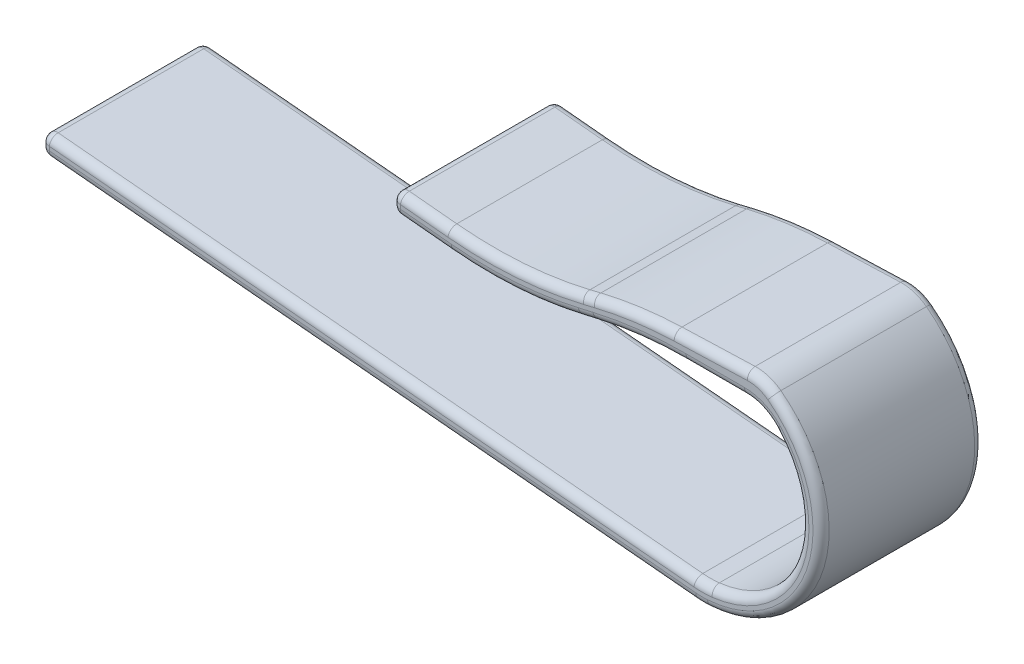
SolidWorks part; units mm, degrees
ref_plane "Front Plane" through (0, 0, 0) normal (0, 0, 1) x (1, 0, 0)
ref_plane "Top Plane" through (0, 0, 0) normal (0, 1, 0) x (1, 0, 0)
ref_plane "Right Plane" through (0, 0, 0) normal (1, 0, 0) x (0, 0, -1)
sketch "Sketch1" plane through (0, 0, 0) normal (0, 0, 1) x (1, 0, 0)
  line L7 (0, -7.5) -> (81.4654, -15)
  line L8 (0, -5) -> (81.4654, -12.5)
  line L11 (0, -5) -> (0, -7.5)
  line L12 (74.0454, 10.0596) -> (88.8853, 10.0596)
  line L13 (73.1738, 12.5) -> (88.8853, 13.0363)
  line L14 (43.4402, 10.4683) -> (43.4402, 7.9683)
  line L15 (43.4402, 10.4683) -> (58.7428, 9.0139)
  line L16 (58.7428, 9.0139) -> (73.1738, 12.5)
  line L17 (43.4402, 7.9683) -> (58.7428, 6.5139)
  line L18 (58.7428, 6.5139) -> (74.0454, 10.0596)
  arc A0 (81.4654, -12.5) -> (88.8853, 10.0596) centre (81.4654, 0) ccw
  arc A1 (81.4654, -15) -> (88.8853, 13.0363) centre (81.4654, 0) ccw
  arc A3 (81.4654, -12.5) -> (88.8853, 10.0596) centre (81.4654, 0) ccw
  arc A4 (81.4654, -15) -> (88.8853, 13.0363) centre (81.4654, 0) ccw
  point P10 (0, 0)
  dimension "D1" = 25
  dimension "D2" = 30
extrude "Boss-Extrude1" add sketch "Sketch1" along normal blind 20 contours L7 A1 L13 L16 L15 L14 L17 L18 L12 A0 L8 L11 region at (1.0046, -6.25, 0)
fillet "Fillet1" radius 50 2 edges at (73.1738, 12.5, 10) (58.7428, 9.0139, 10)
fillet "Fillet2" radius 50 2 edges at (74.0454, 10.0596, 10) (58.7428, 6.5139, 10)
fillet "Fillet3" radius 5 2 edges at (88.8853, 10.0596, 10) (88.8853, 13.0363, 10)
fillet "Fillet4" radius 10 2 edges at (81.4654, -15, 10) (81.4654, -12.5, 10)
fillet "Fillet5" radius 1 4 edges at (43.4402, 7.9683, 10) (43.4402, 10.4683, 10) (0, -7.5, 10) (0, -5, 10)
fillet "Fillet6" radius 1 48 edges at (58.6992, 7.1694, 0) (67.5704, 8.5593, 0) (74.0824, 9.7359, 0) (83.382, 10.0596, 0) (89.0185, 9.6348, 0) (93.1715, -4.3835, 0) (81.859, -12.4832, 0) (40.962, -8.7711, 0) (0.3261, -5.3575, 0) (0, -6.3421, 0) (0.2612, -7.2618, 0) (40.8966, -11.2651, 0) (81.6793, -14.9879, 0) (95.842, -4.2791, 0) (88.9903, 12.7535, 0) (82.7875, 12.8281, 0) (73.2087, 12.2439, 0) (67.5531, 11.1422, 0) (58.6934, 9.7081, 0) (47.4719, 10.0851, 0) (43.7674, 10.1085, 0) (43.4402, 9.1233, 0) (43.7004, 8.2049, 0) (47.4967, 7.5828, 0) (43.7674, 10.1085, 20) (47.4719, 10.0851, 20) (58.6934, 9.7081, 20) (67.5531, 11.1422, 20) (73.2087, 12.2439, 20) (82.7875, 12.8281, 20) (88.9903, 12.7535, 20) (95.842, -4.2791, 20) (81.6793, -14.9879, 20) (40.8966, -11.2651, 20) (0.2612, -7.2618, 20) (0, -6.3421, 20) (0.3261, -5.3575, 20) (40.962, -8.7711, 20) (81.859, -12.4832, 20) (93.1715, -4.3835, 20) (89.0185, 9.6348, 20) (83.382, 10.0596, 20) (74.0824, 9.7359, 20) (67.5704, 8.5593, 20) (58.6992, 7.1694, 20) (47.4967, 7.5828, 20) (43.7004, 8.2049, 20) (43.4402, 9.1233, 20)
